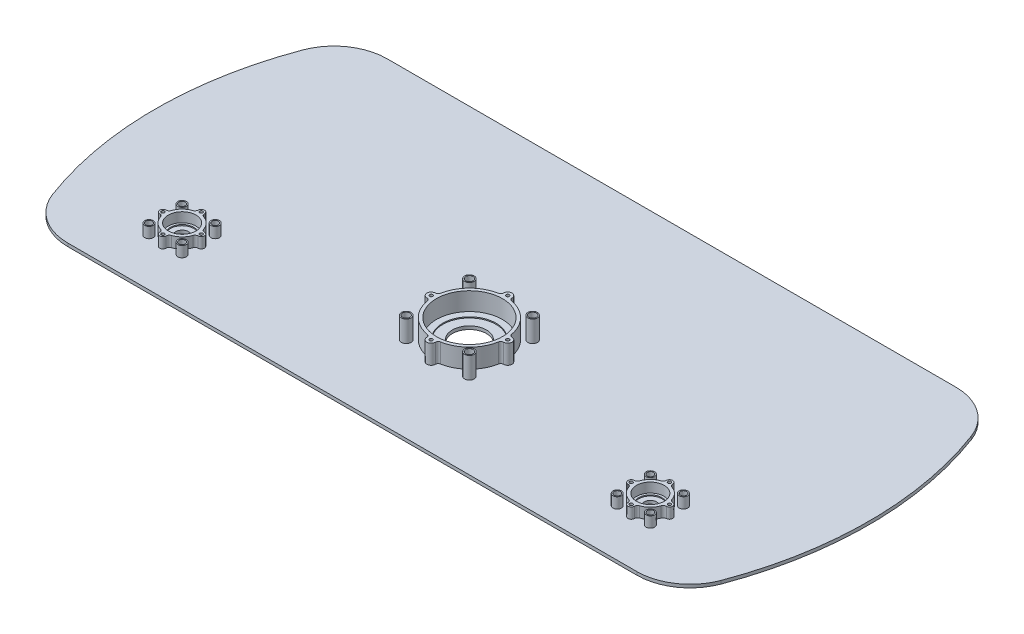
SolidWorks part; units mm, degrees
ref_plane "Front Plane" through (0, 0, 0) normal (0, 0, 1) x (1, 0, 0)
ref_plane "Top Plane" through (0, 0, 0) normal (0, 1, 0) x (1, 0, 0)
ref_plane "Right Plane" through (0, 0, 0) normal (1, 0, 0) x (0, 0, -1)
sketch "Sketch1" plane through (0, 0, 0) normal (0, 1, 0) x (1, 0, 0)
  line L1 (-267.3181, 150) -> (267.3181, 150)
  line L3 (-267.3181, -150) -> (267.3181, -150)
  line L5 (-300, 150) -> (300, -150) construction
  line L6 (-300, -150) -> (300, 150) construction
  arc A0 (314.1486, 117.5186) -> (314.1486, -117.5186) centre (0, 0) cw
  arc A1 (-314.1486, 117.5186) -> (-314.1486, -117.5186) centre (0, 0) ccw
  arc A2 (314.1486, 117.5186) -> (267.3181, 150) centre (267.3181, 100) ccw
  arc A3 (267.3181, -150) -> (314.1486, -117.5186) centre (267.3181, -100) ccw
  arc A4 (-267.3181, -150) -> (-314.1486, -117.5186) centre (-267.3181, -100) cw
  arc A5 (-267.3181, 150) -> (-314.1486, 117.5186) centre (-267.3181, 100) ccw
  circle A6 centre (0, -40) radius 130 construction
  circle A7 centre (-220, -90) radius 60 construction
  circle A8 centre (220, -90) radius 60 construction
  point P0 (0, 0)
  point P19 (0, -40)
  dimension "D3" = 50
  dimension "D5" = 260
  dimension "D6" = 120
  dimension "D7" = 120
  dimension "D1" = 300
  dimension "D2" = 600
  dimension "D4" = 40
  dimension "D8" = 90
  dimension "D9" = 220
  dimension "D10" = 90
  dimension "D11" = 220
extrude "Boss-Extrude1" add sketch "Sketch1" along normal blind 3
sketch "Sketch2" plane through (0, 3, 0) normal (0, 1, 0) x (1, 0, 0)
  circle A0 centre (220, -90) radius 60 construction
  circle A1 centre (-220, -90) radius 60 construction
  circle A2 centre (220, -90) radius 60 construction
  circle A3 centre (-220, -90) radius 60 construction
  circle A4 centre (-220, -90) radius 6
  circle A5 centre (220, -90) radius 6
  circle A6 centre (0, -40) radius 17.5
  circle A7 centre (220, -90) radius 11
  circle A8 centre (220, -90) radius 13
  circle A9 centre (-220, -90) radius 13
  circle A10 centre (-220, -90) radius 11
  circle A13 centre (-220, -90) radius 16
  circle A14 centre (220, -90) radius 16
  circle A15 centre (238, -90) radius 1.5
  arc A16 (235.8611, -87.8964) -> (235.8611, -92.1036) centre (238, -90) cw
  arc A17 (222.1036, -105.8611) -> (217.8964, -105.8611) centre (220, -108) cw
  circle A18 centre (220, -108) radius 1.5
  arc A19 (204.1389, -92.1036) -> (204.1389, -87.8964) centre (202, -90) cw
  circle A20 centre (202, -90) radius 1.5
  arc A21 (217.8964, -74.1389) -> (222.1036, -74.1389) centre (220, -72) cw
  circle A22 centre (220, -72) radius 1.5
  arc A23 (202, -87) -> (204.8114, -84.9696) centre (202, -84.0385) ccw
  arc A24 (202, -93) -> (204.8114, -95.0304) centre (202, -95.9615) cw
  arc A25 (223, -72) -> (225.0304, -74.8114) centre (225.9615, -72) ccw
  arc A26 (217, -72) -> (214.9696, -74.8114) centre (214.0385, -72) cw
  arc A27 (238, -93) -> (235.1886, -95.0304) centre (238, -95.9615) ccw
  arc A28 (238, -87) -> (235.1886, -84.9696) centre (238, -84.0385) cw
  arc A29 (217, -108) -> (214.9696, -105.1886) centre (214.0385, -108) ccw
  arc A30 (223, -108) -> (225.0304, -105.1886) centre (225.9615, -108) cw
  point P36 (220, -90)
  point P61 (220, -90)
  dimension "D1" = 35
  dimension "D2" = 26
  dimension "D3" = 22
  dimension "D4" = 26
  dimension "D5" = 22
  dimension "D6" = 12
  dimension "D7" = 12
  dimension "D8" = 3
  dimension "D9" = 3
  dimension "D10" = 3
  dimension "D11" = 18
  dimension "D12" = 4
  dimension "D13" = 4
extrude "Cut-Extrude1" cut sketch "Sketch2" against normal blind 10 contours A4 | A5 region at (-220, 3, 90) region at (220, 3, 90)
extrude "Boss-Extrude2" add sketch "Sketch2<3>" along normal blind 1 from surface contours A9 A10 | A8 A7 region at (207.3677, 3, 90) region at (-232.6323, 3, 90) starting at face at (-220, 3, 96)
sketch "Sketch2<3>" plane through (0, 3, 0) normal (0, 1, 0) x (1, 0, 0) same geometry as "Sketch2"
extrude "Boss-Extrude3" add sketch "Sketch2<4>" along normal blind 10 from surface contours A14 A8 | A19 A14 A20 | A21 A14 A22 | A16 A14 A15 | A17 A14 A18 | A23 A19 A14 | A19 A24 A14 | A25 A21 A14 | A21 A26 A14 | A16 A28 A14 | A27 A16 A14 | A17 A30 A14 | A29 A17 A14 region at (235.5137, 3, 91.0243) region at (236.0441, 3, 88.9407) region at (236.2045, 3, 86.846) region at (236.2045, 3, 93.154) region at (223.154, 3, 73.7955) region at (223.154, 3, 106.2045) region at (220, 3, 73.921) region at (222.694, 3, 106.871) region at (216.846, 3, 73.7955) region at (216.846, 3, 106.2045) region at (203.7955, 3, 86.846) region at (203.7955, 3, 93.154) region at (203.921, 3, 90) starting at face at (220, 3, 103)
sketch "Sketch2<4>" plane through (0, 3, 0) normal (0, 1, 0) x (1, 0, 0) same geometry as "Sketch2"
sketch "Sketch3" plane through (0, 3, 0) normal (0, 1, 0) x (1, 0, 0)
  circle A0 centre (0, -40) radius 16
  circle A1 centre (0, -40) radius 25
  circle A2 centre (0, -40) radius 31
  circle A3 centre (0, -40) radius 34
  circle A4 centre (36, -40) radius 1.5
  arc A6 (33.8333, -43.3624) -> (33.8333, -36.6376) centre (36, -40) ccw
  arc A7 (-3.3624, -73.8333) -> (3.3624, -73.8333) centre (0, -76) ccw
  circle A8 centre (0, -76) radius 1.5
  arc A9 (-33.8333, -36.6376) -> (-33.8333, -43.3624) centre (-36, -40) ccw
  circle A10 centre (-36, -40) radius 1.5
  arc A11 (3.3624, -6.1667) -> (-3.3624, -6.1667) centre (0, -4) ccw
  circle A12 centre (0, -4) radius 1.5
  arc A13 (-36, -36) -> (-33.4426, -33.8689) centre (-36, -33.4) ccw
  arc A14 (-36, -44) -> (-33.4426, -46.1311) centre (-36, -46.6) cw
  arc A15 (4, -4) -> (6.1311, -6.5574) centre (6.6, -4) ccw
  arc A16 (-4, -4) -> (-6.1311, -6.5574) centre (-6.6, -4) cw
  arc A17 (36, -44) -> (33.4426, -46.1311) centre (36, -46.6) ccw
  arc A18 (36, -36) -> (33.4426, -33.8689) centre (36, -33.4) cw
  arc A19 (-4, -76) -> (-6.1311, -73.4426) centre (-6.6, -76) ccw
  arc A20 (4, -76) -> (6.1311, -73.4426) centre (6.6, -76) cw
  point P25 (0, -40)
  point P50 (0, -40)
  dimension "D1" = 32
  dimension "D2" = 62
  dimension "D3" = 3
  dimension "D4" = 50
  dimension "D5" = 4
  dimension "D7" = 3
  dimension "D6" = 36
  dimension "D8" = 4
  dimension "D9" = 4
extrude "Cut-Extrude8" cut sketch "Sketch3" against normal blind 10 contours A0 region at (0, 3, 40)
extrude "Boss-Extrude4" add sketch "Sketch3<3>" along normal blind 1 from surface contours A2 A1 region at (-30.1232, 3, 40) starting at face at (0, 3, 56)
sketch "Sketch3<3>" plane through (0, 3, 0) normal (0, 1, 0) x (1, 0, 0) same geometry as "Sketch3"
extrude "Boss-Extrude5" add sketch "Sketch3<4>" along normal blind 18 from surface contours A3 A2 | A3 A6 A4 | A3 A7 A8 | A3 A9 A10 | A3 A11 A12 | A13 A9 A3 | A9 A14 A3 | A11 A16 A3 | A15 A11 A3 | A17 A6 A3 | A6 A18 A3 | A7 A20 A3 | A19 A7 A3 region at (32.9978, 3, 41.6356) region at (34.0592, 3, 38.3117) region at (34.2416, 3, 35.7431) region at (34.2416, 3, 44.2569) region at (4.2569, 3, 5.7584) region at (4.2569, 3, 74.2416) region at (0, 3, 5.899) region at (3.7404, 3, 74.8992) region at (-4.2569, 3, 5.7584) region at (-4.2569, 3, 74.2416) region at (-34.2416, 3, 35.7431) region at (-34.2416, 3, 44.2569) region at (-34.101, 3, 40) starting at face at (0, 3, 71)
sketch "Sketch3<4>" plane through (0, 3, 0) normal (0, 1, 0) x (1, 0, 0) same geometry as "Sketch3"
mirror "Mirror1" about plane through (0, 0, 0) normal (1, 0, 0) of "Boss-Extrude3"
sketch "Sketch4" plane through (0, 3, 0) normal (0, 1, 0) x (1, 0, 0)
  line B0 (0, -40) -> (-78.0469, 38.0469) construction
  circle B1 centre (-29.6985, -10.3015) radius 2
  circle B2 centre (-29.6985, -10.3015) radius 4.5
  circle B3 centre (-29.6985, -10.3015) radius 3.5
  circle B4 centre (29.6985, -10.3015) radius 4.5
  circle B5 centre (29.6985, -10.3015) radius 3.5
  circle B6 centre (29.6985, -10.3015) radius 2
  circle B7 centre (29.6985, -69.6985) radius 4.5
  circle B8 centre (29.6985, -69.6985) radius 3.5
  circle B9 centre (29.6985, -69.6985) radius 2
  circle B10 centre (-29.6985, -69.6985) radius 4.5
  circle B11 centre (-29.6985, -69.6985) radius 3.5
  circle B12 centre (-29.6985, -69.6985) radius 2
  circle B13 centre (-29.6985, -10.3015) radius 6.5
  arc B14 (-31.7007, -27.4352) -> (-34.2947, -14.8977) centre (-42.5371, -23.1401) ccw
  arc B15 (-12.5648, -8.2993) -> (-25.1023, -5.7053) centre (-16.8599, 2.5371) cw
  arc B16 (12.5648, -8.2993) -> (25.1023, -5.7053) centre (16.8599, 2.5371) ccw
  arc B17 (31.7007, -27.4352) -> (34.2947, -14.8977) centre (42.5371, -23.1401) cw
  circle B18 centre (29.6985, -10.3015) radius 6.5
  arc B19 (31.7007, -52.5648) -> (34.2947, -65.1023) centre (42.5371, -56.8599) ccw
  arc B20 (12.5648, -71.7007) -> (25.1023, -74.2947) centre (16.8599, -82.5371) cw
  circle B21 centre (29.6985, -69.6985) radius 6.5
  arc B22 (-12.5648, -71.7007) -> (-25.1023, -74.2947) centre (-16.8599, -82.5371) ccw
  arc B23 (-31.7007, -52.5648) -> (-34.2947, -65.1023) centre (-42.5371, -56.8599) cw
  circle B24 centre (-29.6985, -69.6985) radius 6.5
  circle B25 centre (0, -40) radius 34.1
  circle B26 centre (3.6047, -60.6883) radius 2.7
  circle B27 centre (-19.7189, -32.7776) radius 2.7
  circle B28 centre (16.1143, -26.5341) radius 2.7
  circle B29 centre (0, -40) radius 6.5
sketch_block_instance "Block2-1"
sketch_block "Block2" parameters "D1"=4, "D2"=7, "D3"=9, "D4"=13
sketch_block_instance "Block1-1"
sketch_block "Block1"
extrude "Boss-Extrude6" add sketch "Sketch4" along normal blind 20 contours B4 B5 | B5 B6 | B2 B3 | B3 B1 | B7 B8 | B8 B9 | B10 B11 | B11 B12 region at (-34.0712, 3, 10.3015) region at (-33.0995, 3, 10.3015) region at (25.3258, 3, 10.3015) region at (26.2975, 3, 10.3015) region at (25.3258, 3, 69.6985) region at (26.2975, 3, 69.6985) region at (-34.0712, 3, 69.6985) region at (-33.0995, 3, 69.6985)
extrude "Cut-Extrude9" cut sketch "Sketch4<3>" against normal blind 5 from surface contours B3 B1 | B5 B6 | B8 B9 | B11 B12 region at (-33.0995, 3, 10.3015) region at (26.2975, 3, 10.3015) region at (26.2975, 3, 69.6985) region at (-33.0995, 3, 69.6985) starting at face at (-29.6985, 23, 14.8015)
sketch "Sketch4<3>" plane through (0, 3, 0) normal (0, 1, 0) x (1, 0, 0) same geometry as "Sketch4"
sketch "Sketch5" plane through (0, 3, 0) normal (0, 1, 0) x (1, 0, 0)
  circle B0 centre (204.4437, -74.4437) radius 1.5
  circle B1 centre (204.4437, -74.4437) radius 3
  circle B2 centre (204.4437, -74.4437) radius 4
  circle B3 centre (204.4437, -105.5563) radius 1.5
  arc B4 (200.5546, -101.6673) -> (208.3327, -109.4454) centre (204.4437, -105.5563) ccw
  arc B5 (218.4477, -105.824) -> (208.3327, -109.4454) centre (217.2205, -118.3332) ccw
  arc B6 (218.4477, -105.824) -> (221.5523, -105.824) centre (220, -90) ccw
  arc B7 (231.6673, -109.4454) -> (221.5523, -105.824) centre (222.7795, -118.3332) ccw
  arc B8 (231.6673, -109.4454) -> (239.4454, -101.6673) centre (235.5563, -105.5563) ccw
  arc B9 (235.824, -91.5523) -> (239.4454, -101.6673) centre (248.3332, -92.7795) ccw
  arc B10 (235.824, -91.5523) -> (235.824, -88.4477) centre (220, -90) ccw
  arc B11 (239.4454, -78.3327) -> (235.824, -88.4477) centre (248.3332, -87.2205) ccw
  arc B12 (239.4454, -78.3327) -> (231.6673, -70.5546) centre (235.5563, -74.4437) ccw
  arc B13 (221.5523, -74.176) -> (231.6673, -70.5546) centre (222.7795, -61.6668) ccw
  arc B14 (221.5523, -74.176) -> (218.4477, -74.176) centre (220, -90) ccw
  arc B15 (208.3327, -70.5546) -> (218.4477, -74.176) centre (217.2205, -61.6668) ccw
  arc B16 (208.3327, -70.5546) -> (200.5546, -78.3327) centre (204.4437, -74.4437) ccw
  arc B17 (204.176, -88.4477) -> (200.5546, -78.3327) centre (191.6668, -87.2205) ccw
  arc B18 (204.176, -88.4477) -> (204.176, -91.5523) centre (220, -90) ccw
  arc B19 (200.5546, -101.6673) -> (204.176, -91.5523) centre (191.6668, -92.7795) ccw
  circle B20 centre (204.4437, -105.5563) radius 3
  circle B21 centre (204.4437, -105.5563) radius 4
  circle B22 centre (235.5563, -105.5563) radius 1.5
  circle B23 centre (235.5563, -105.5563) radius 3
  circle B24 centre (235.5563, -105.5563) radius 4
  circle B25 centre (235.5563, -74.4437) radius 1.5
  circle B26 centre (235.5563, -74.4437) radius 3
  circle B27 centre (235.5563, -74.4437) radius 4
sketch_block_instance "Block3-1"
sketch_block "Block3"
extrude "Boss-Extrude7" add sketch "Sketch5" along normal blind 10 contours B27 B26 | B26 B25 | B2 B1 | B1 B0 | B24 B23 | B23 B22 | B20 B3 | B21 B20 region at (201.5285, 3, 74.4437) region at (200.5568, 3, 74.4437) region at (201.5285, 3, 105.5563) region at (200.5568, 3, 105.5563) region at (232.6412, 3, 105.5563) region at (231.6695, 3, 105.5563) region at (232.6412, 3, 74.4437) region at (231.6695, 3, 74.4437)
extrude "Cut-Extrude10" cut sketch "Sketch5<3>" against normal blind 5 from surface contours B20 B3 | B1 B0 | B26 B25 | B23 B22 region at (201.5285, 3, 74.4437) region at (201.5285, 3, 105.5563) region at (232.6412, 3, 105.5563) region at (232.6412, 3, 74.4437) starting at face at (235.5563, 13, 109.5563)
sketch "Sketch5<3>" plane through (0, 3, 0) normal (0, 1, 0) x (1, 0, 0) same geometry as "Sketch5"
mirror "Mirror2" about plane through (0, 0, 0) normal (1, 0, 0) of "Boss-Extrude7", "Cut-Extrude10"
sketch "Sketch6" plane through (0, 0, 0) normal (0, -1, 0) x (1, 0, 0)
  point P0 (0, 0)
  line B0 (220, 60) -> (-220, 60)
  line B1 (220, 120) -> (-220, 120)
  line B2 (220, 122) -> (-220, 122)
  line B3 (220, 58) -> (-220, 58)
  arc B4 (220, 120) -> (220, 60) centre (220, 90) cw
  arc B5 (-220, 120) -> (-220, 60) centre (-220, 90) ccw
  arc B6 (-220, 122) -> (-220, 58) centre (-220, 90) ccw
  arc B7 (220, 122) -> (220, 58) centre (220, 90) cw
  circle B8 centre (0, 118) radius 2
  circle B9 centre (0, 62) radius 2
  arc B10 (-4.5826, 120) -> (4.5826, 120) centre (0, 118) ccw
  arc B11 (-4.5826, 60) -> (4.5826, 60) centre (0, 62) cw
  arc B12 (105.4174, 120) -> (114.5826, 120) centre (110, 118) ccw
  arc B13 (107.1277, 120) -> (112.8723, 120) centre (110, 118) ccw
  arc B14 (-112.8723, 60) -> (-107.1277, 60) centre (-110, 62) ccw
  arc B15 (-112.8723, 60) -> (-107.1277, 60) centre (-110, 62) cw
  circle B16 centre (110, 118) radius 2
  arc B17 (107.1277, 120) -> (112.8723, 120) centre (110, 118) cw
  arc B18 (-2.8723, 120) -> (2.8723, 120) centre (0, 118) ccw
  arc B19 (-2.8723, 60) -> (2.8723, 60) centre (0, 62) cw
  arc B20 (107.1277, 60) -> (112.8723, 60) centre (110, 62) ccw
  circle B21 centre (110, 62) radius 2
  arc B22 (107.1277, 60) -> (112.8723, 60) centre (110, 62) cw
  arc B23 (105.4174, 60) -> (114.5826, 60) centre (110, 62) cw
  arc B24 (-114.5826, 60) -> (-105.4174, 60) centre (-110, 62) cw
  circle B25 centre (-110, 62) radius 2
  circle B26 centre (-110, 118) radius 2
  arc B27 (-112.8723, 120) -> (-107.1277, 120) centre (-110, 118) ccw
  arc B28 (-114.5826, 120) -> (-105.4174, 120) centre (-110, 118) ccw
  arc B29 (-112.8723, 120) -> (-107.1277, 120) centre (-110, 118) cw
  arc B30 (-2.8723, 60) -> (2.8723, 60) centre (0, 62) ccw
  arc B31 (-2.8723, 120) -> (2.8723, 120) centre (0, 118) cw
  arc B32 (-222.8723, 60) -> (-217.1277, 60) centre (-220, 62) ccw
  arc B33 (-222.8723, 60) -> (-217.1277, 60) centre (-220, 62) cw
  arc B34 (-224.7286, 60.375) -> (-215.4174, 60) centre (-220, 62) cw
  circle B35 centre (-220, 62) radius 2
  circle B36 centre (-220, 118) radius 2
  arc B37 (-222.8723, 120) -> (-217.1277, 120) centre (-220, 118) ccw
  arc B38 (-224.7286, 119.625) -> (-215.4174, 120) centre (-220, 118) ccw
  arc B39 (-222.8723, 120) -> (-217.1277, 120) centre (-220, 118) cw
  arc B40 (215.4174, 120) -> (224.7286, 119.625) centre (220, 118) ccw
  arc B41 (217.1277, 120) -> (222.8723, 120) centre (220, 118) ccw
  circle B42 centre (220, 118) radius 2
  arc B43 (217.1277, 120) -> (222.8723, 120) centre (220, 118) cw
  arc B44 (217.1277, 60) -> (222.8723, 60) centre (220, 62) ccw
  circle B45 centre (220, 62) radius 2
  arc B46 (217.1277, 60) -> (222.8723, 60) centre (220, 62) cw
  arc B47 (215.4174, 60) -> (224.7286, 60.375) centre (220, 62) cw
sketch_block_instance "Block4-1"
sketch_block "Block4" parameters "D3"=4, "D6"=4, "D1"=30, "D2"=30, "D4"=7, "D5"=3, "D7"=1.5, "D8"=110, "D9"=110
